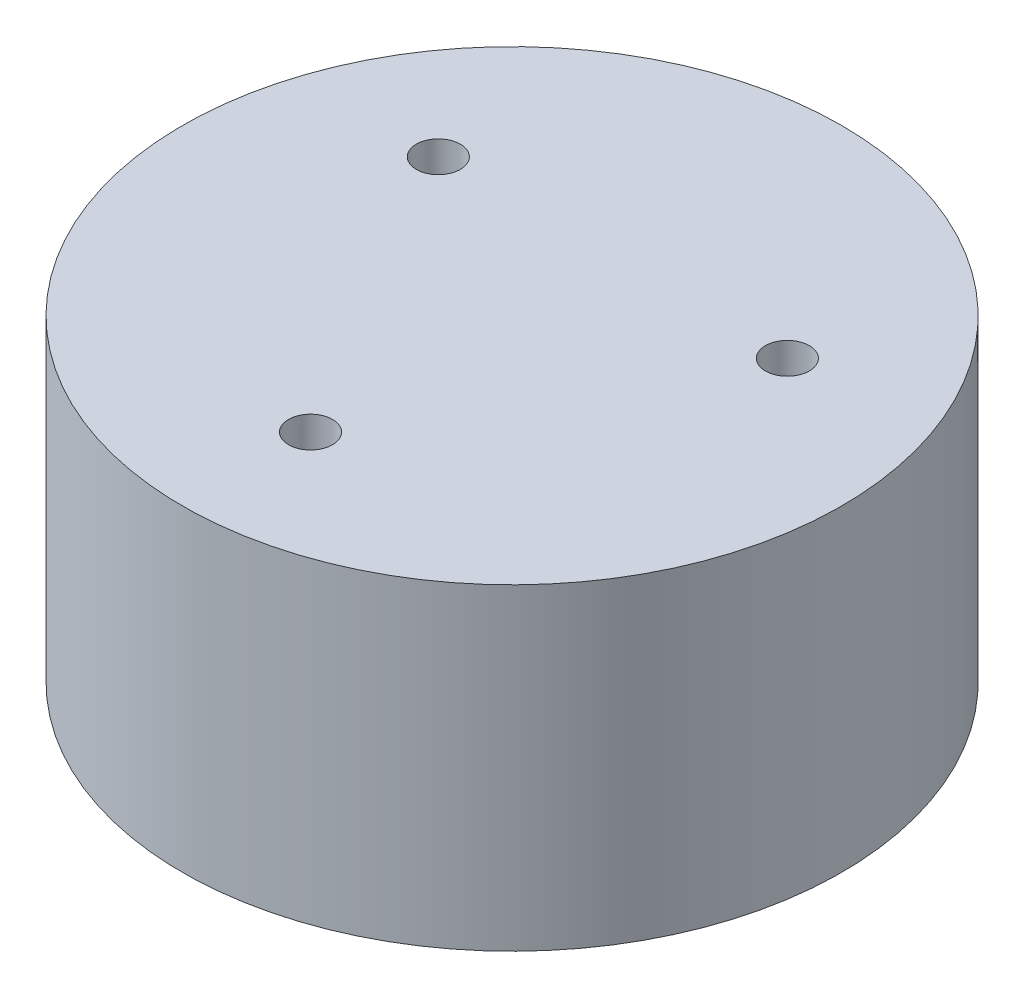
SolidWorks part; units mm, degrees
ref_plane "Front Plane" through (0, 0, 0) normal (0, 0, 1) x (1, 0, 0)
ref_plane "Top Plane" through (0, 0, 0) normal (0, 1, 0) x (1, 0, 0)
ref_plane "Right Plane" through (0, 0, 0) normal (1, 0, 0) x (0, 0, -1)
sketch "Sketch2" plane through (0, 0, 0) normal (0, 1, 0) x (1, 0, 0)
  circle A0 centre (0, 0) radius 27
  dimension "D1" = 54
extrude "Boss-Extrude2" add sketch "Sketch2" along normal blind 26
sketch "Sketch6" plane through (0, 0, 0) normal (0, -1, 0) x (-1, 0, 0)
  line L0 (-14.2981, 8.255) -> (0, 0) construction
  line L1 (0, 0) -> (14.2981, 8.255) construction
  line L3 (0, 0) -> (0, -16.51) construction
  point P0 (0, -16.51)
  point P2 (-14.2981, 8.255)
  point P4 (14.2981, 8.255)
  dimension "D1" = 16.51
  dimension "D2" = 120
  dimension "D3" = 120
hole_wizard "CBORE for M3 SHCS1" positions "Sketch6" profile "Sketch5" counterbore size "M3" standard "ANSI Metric" end condition through all
sketch "Sketch5" plane through (0, 0, 16.51) normal (1, 0, 0) x (0, 0, -1)
  line L0 (0, 0) -> (0, 26)
  line L1 (0, 26) -> (1.8, 26)
  line L3 (1.8, 26) -> (1.8, 18)
  line L4 (3.25, 18) -> (1.8, 18)
  line L5 (3.25, 18) -> (3.25, 0.025)
  line L6 (3.25, 0.025) -> (3.275, 0)
  line L7 (3.275, 0) -> (0, 0)
  line L8 (-3.25, 0.025) -> (-3.275, 0) construction
  line L11 (0, -6.35) -> (0, 107.95) construction
  dimension "Thru Hole Dia." = 3.6
  dimension "Thru Hole Depth" = 26
  dimension "C'Bore Dia." = 6.5
  dimension "C'Bore Depth" = 18
  dimension "Near C'Sink Dia." = 6.55
  dimension "Near C'Sink Angle" = 90
sketch "Sketch9" plane through (0, 0, 0) normal (0, -1, 0) x (-1, 0, 0)
  line L0 (-14.2981, -8.255) -> (0, 0) construction
  line L1 (0, 0) -> (0, 16.51) construction
  line L2 (0, 0) -> (14.2981, -8.255) construction
  point P0 (14.2981, -8.255)
  point P2 (0, 16.51)
  point P4 (-14.2981, -8.255)
  dimension "D1" = 120
  dimension "D2" = 120
  dimension "D3" = 16.51
hole_wizard "Hole1" positions "Sketch9" profile "Sketch8" legacy
sketch "Sketch8" plane through (-14.2981, 0, 8.255) normal (1, 0, 0) x (0, 0, -1)
  line L0 (0, 0) -> (0, 15)
  line L1 (0, 15) -> (3.2, 15)
  line L2 (3.2, 15) -> (3.2, 2)
  line L3 (3.2, 2) -> (3.65, 2)
  line L4 (3.65, 2) -> (3.65, 0)
  line L5 (3.65, 0) -> (0, 0)
  line L6 (0, 110) -> (0, -10) construction
  dimension "Diameter" = 6.4
  dimension "Depth" = 15
  dimension "C-Bore Diameter" = 7.3
  dimension "C-Bore Depth" = 2
chamfer "Chamfer1" distance 2 distance2 0.45 3 edges at (-14.2981, 2, 4.605) (0, 2, -20.16) (14.2981, 2, 4.605) first distance on face at (-14.2981, 2, 4.605) first distance on face at (0, 2, -20.16) first distance on face at (14.2981, 2, 4.605)
